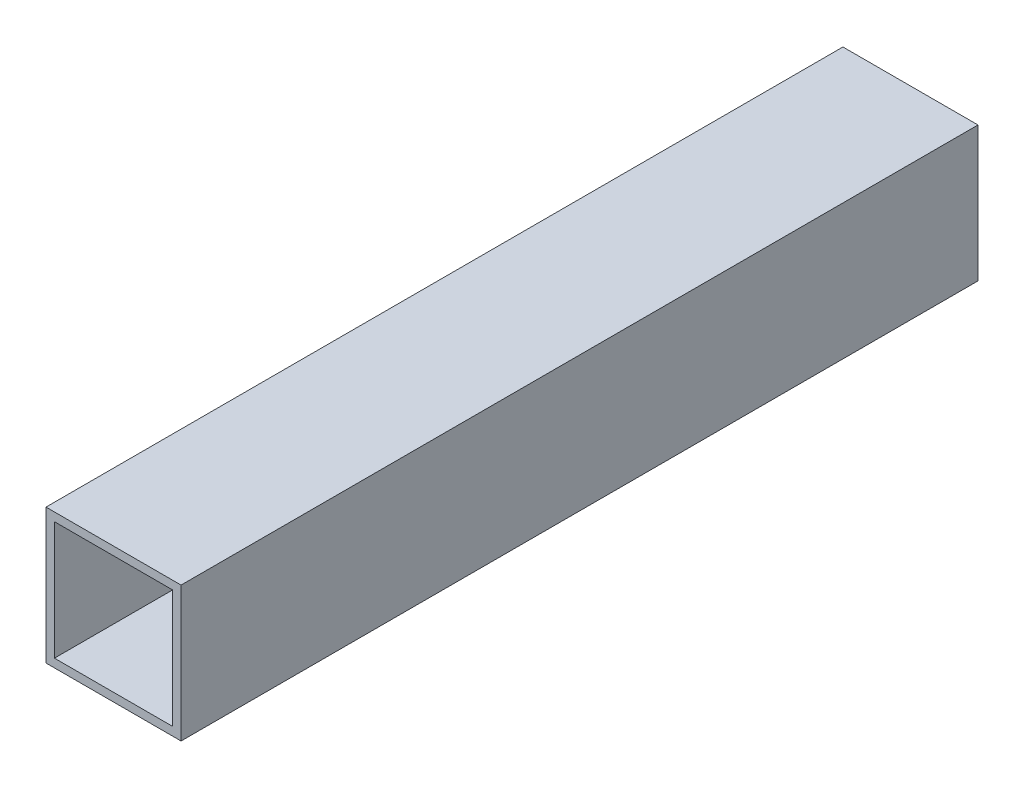
SolidWorks part; units mm, degrees
ref_plane "Front Plane" through (0, 0, 0) normal (0, 0, 1) x (1, 0, 0)
ref_plane "Top Plane" through (0, 0, 0) normal (0, 1, 0) x (1, 0, 0)
ref_plane "Right Plane" through (0, 0, 0) normal (1, 0, 0) x (0, 0, -1)
sketch "Sketch1" plane through (0, 0, 0) normal (0, 0, 1) x (1, 0, 0)
  line L1 (-12.7, -12.7) -> (12.7, -12.7)
  line L2 (-12.7, -12.7) -> (-12.7, 12.7)
  line L3 (-12.7, 12.7) -> (12.7, 12.7)
  line L4 (12.7, -12.7) -> (12.7, 12.7)
  line L5 (-12.7, -12.7) -> (12.7, 12.7) construction
  line L6 (-12.7, 12.7) -> (12.7, -12.7) construction
  point P0 (0, 0)
  dimension "D1" = 25.4
  dimension "D2" = 25.4
extrude "Boss-Extrude1" add sketch "Sketch1" along normal mid plane 149.86
shell "Shell1" thickness 1.5875 removed face at (0, 0, -74.93) removed face at (0, 0, 74.93)
